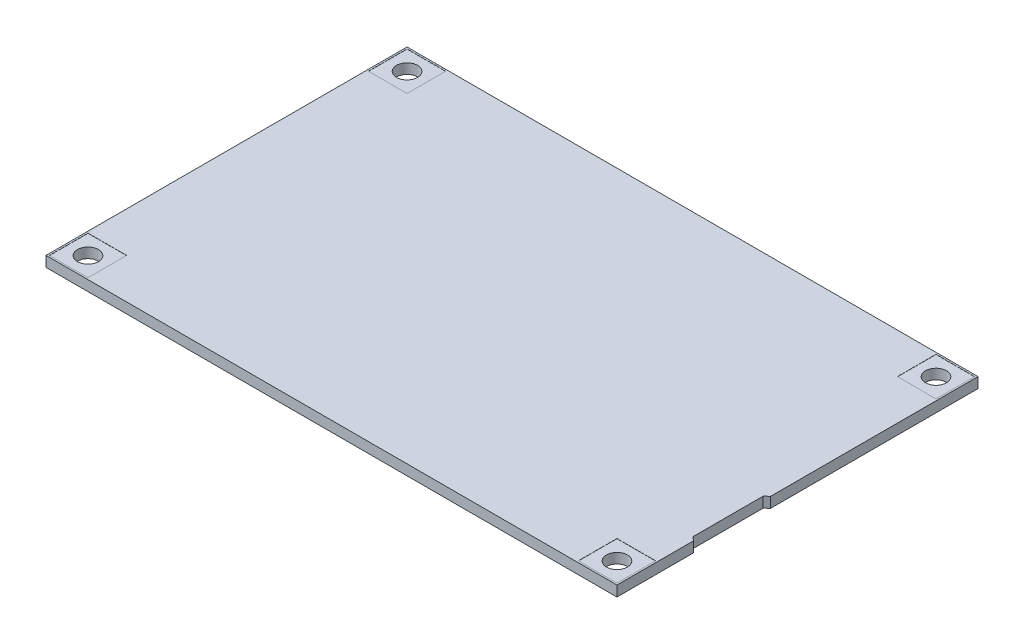
SolidWorks part; units mm, degrees
ref_plane "Front Plane" through (0, 0, 0) normal (0, 0, 1) x (1, 0, 0)
ref_plane "Top Plane" through (0, 0, 0) normal (0, 1, 0) x (1, 0, 0)
ref_plane "Right Plane" through (0, 0, 0) normal (1, 0, 0) x (0, 0, -1)
sketch "Sketch1" plane through (0, 0, 0) normal (0, 1, 0) x (1, 0, 0)
  line L0 (85.774, 22.699) -> (85.774, 12.099)
  line L1 (0, 0) -> (86.36, 0)
  line L2 (0, 0) -> (0, 54.61)
  line L3 (0, 54.61) -> (86.36, 54.61)
  line L4 (86.36, 0) -> (86.36, 11.557)
  line L5 (85.774, 12.099) -> (86.36, 11.557)
  line L6 (85.774, 22.699) -> (86.36, 23.241)
  line L7 (86.36, 23.241) -> (86.36, 54.61)
  circle A0 centre (3.175, 51.435) radius 1.5875
  circle A1 centre (3.175, 3.175) radius 1.5875
  circle A2 centre (83.185, 3.175) radius 1.5875
  circle A3 centre (83.185, 51.435) radius 1.5875
  dimension "D7" = 3.175
  dimension "D1" = 86.36
  dimension "D2" = 54.61
  dimension "D3" = 0.586
  dimension "D4" = 11.557
  dimension "D5" = 10.5999
  dimension "D6" = 31.369
  dimension "D8" = 3.175
  dimension "D9" = 3.175
  dimension "D10" = 3.175
  dimension "D11" = 3.175
extrude "Boss-Extrude1" add sketch "Sketch1" along normal blind 1.5748
sketch "Sketch2" plane through (0, 1.5748, 0) normal (0, 1, 0) x (1, 0, 0)
  line L0 (3.175, 54.356) -> (3.175, 48.514) construction
  line L1 (0.254, 54.356) -> (6.096, 54.356)
  line L2 (0.254, 54.356) -> (0.254, 48.514)
  line L3 (0.254, 48.514) -> (6.096, 48.514)
  line L4 (6.096, 54.356) -> (6.096, 48.514)
  line L5 (0.254, 6.096) -> (6.096, 6.096)
  line L6 (0.254, 6.096) -> (0.254, 0.254)
  line L7 (0.254, 0.254) -> (6.096, 0.254)
  line L8 (6.096, 6.096) -> (6.096, 0.254)
  line L9 (80.264, 6.096) -> (86.106, 6.096)
  line L10 (80.264, 6.096) -> (80.264, 0.254)
  line L11 (80.264, 0.254) -> (86.106, 0.254)
  line L12 (86.106, 6.096) -> (86.106, 0.254)
  line L13 (80.264, 54.356) -> (86.106, 54.356)
  line L14 (80.264, 54.356) -> (80.264, 48.514)
  line L15 (80.264, 48.514) -> (86.106, 48.514)
  line L16 (86.106, 54.356) -> (86.106, 48.514)
  line L17 (3.175, 0.254) -> (3.175, 6.096) construction
  line L18 (83.185, 6.096) -> (83.185, 0.254) construction
  circle A0 centre (3.175, 51.435) radius 1.5875 construction
  circle A1 centre (3.175, 3.175) radius 1.5875 construction
  circle A2 centre (83.185, 3.175) radius 1.5875 construction
  point P18 (3.175, 51.435)
  point P23 (3.175, 3.175)
  point P28 (83.185, 3.175)
  dimension "D1" = 5.842
extrude "Cut-Extrude1" cut sketch "Sketch2" against normal blind 0.0254
extrude "Cut-Extrude2" cut sketch "Sketch2<2>" along normal blind 0.0254 from surface starting at face at (83.185, 0, -1.5875)
sketch "Sketch2<2>" plane through (0, 1.5748, 0) normal (0, 1, 0) x (1, 0, 0) same geometry as "Sketch2"
